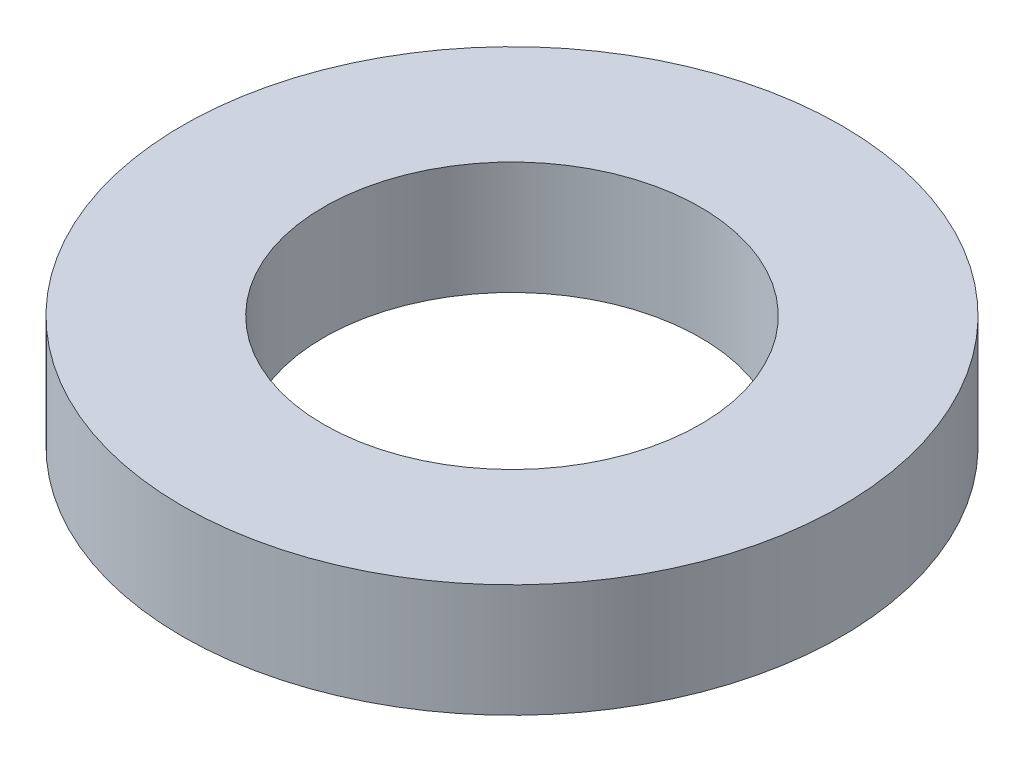
SolidWorks part; units mm, degrees
ref_plane "Front Plane" through (0, 0, 0) normal (0, 0, 1) x (1, 0, 0)
ref_plane "Top Plane" through (0, 0, 0) normal (0, 1, 0) x (1, 0, 0)
ref_plane "Right Plane" through (0, 0, 0) normal (1, 0, 0) x (0, 0, -1)
sketch "Sketch1" plane through (0, 0, 0) normal (0, 1, 0) x (1, 0, 0)
  circle A0 centre (0, 0) radius 52.5
  dimension "FLANGE_OD" = 105
extrude "Boss-Extrude1" add sketch "Sketch1" along normal blind 18
sketch "Sketch2" plane through (0, 0, 0) normal (0, 1, 0) x (1, 0, 0)
  circle A0 centre (0, 0) radius 30
  dimension "BORE_D" = 60
extrude "Cut-Extrude1" cut sketch "Sketch2" along normal through all
sketch "Sketch3" plane through (0, 18, 0) normal (0, 1, 0) x (1, 0, 0)
  circle A0 centre (0, 0) radius 24.4072 construction
  circle A1 centre (-24.4072, 0) radius 1.6336
  dimension "BOLT_D" = 3.2672
  dimension "BOLT_PCD" = 48.8145
extrude "Cut-Extrude2" cut sketch "Sketch3" against normal blind 12.8069 rebuild error yes
pattern_circular "CirPattern1" count 6 over 360 rebuild error yes
